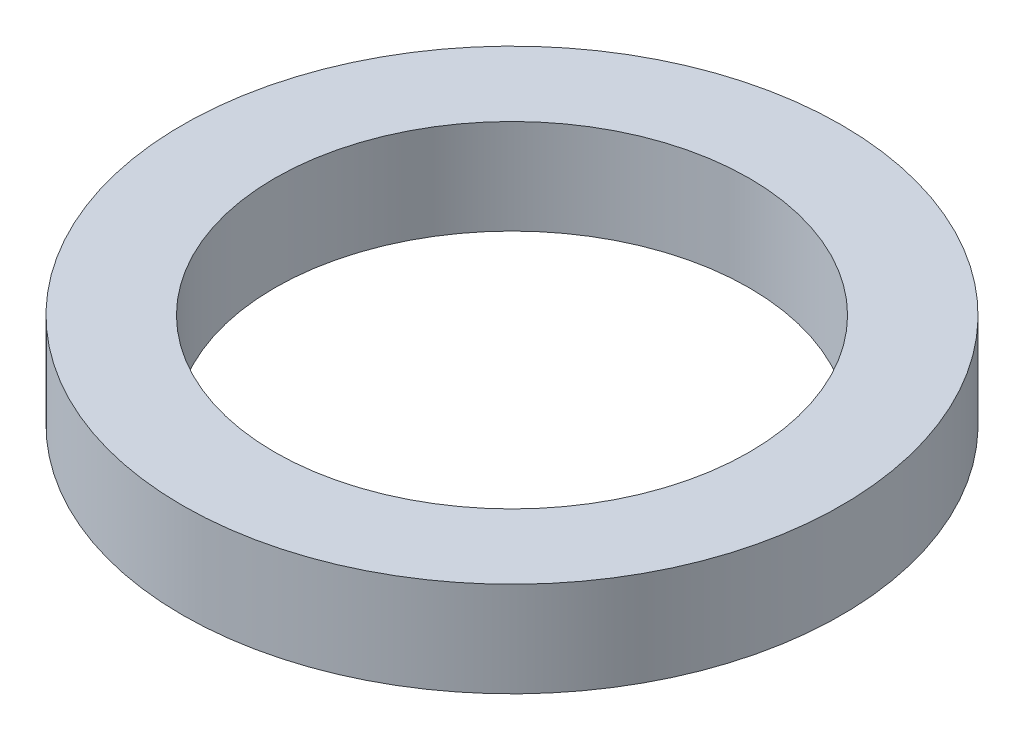
SolidWorks part; units mm, degrees
ref_plane "Front Plane" through (0, 0, 0) normal (0, 0, 1) x (1, 0, 0)
ref_plane "Top Plane" through (0, 0, 0) normal (0, 1, 0) x (1, 0, 0)
ref_plane "Right Plane" through (0, 0, 0) normal (1, 0, 0) x (0, 0, -1)
sketch "Sketch1" plane through (0, 0, 0) normal (0, 1, 0) x (1, 0, 0)
  circle A0 centre (0, 0) radius 62.5
  dimension "FLANGE_OD" = 125
extrude "Boss-Extrude1" add sketch "Sketch1" along normal blind 18
sketch "Sketch2" plane through (0, 0, 0) normal (0, 1, 0) x (1, 0, 0)
  circle A0 centre (0, 0) radius 45
  dimension "BORE_D" = 90
extrude "Cut-Extrude1" cut sketch "Sketch2" along normal through all
sketch "Sketch3" plane through (0, 18, 0) normal (0, 1, 0) x (1, 0, 0)
  circle A0 centre (0, 0) radius 28.2792 construction
  circle A1 centre (-28.2792, 0) radius 2.3091
  dimension "BOLT_D" = 4.6182
  dimension "BOLT_PCD" = 56.5584
extrude "Cut-Extrude2" cut sketch "Sketch3" against normal blind 12.1144 rebuild error yes
pattern_circular "CirPattern1" count 6 over 360 rebuild error yes
